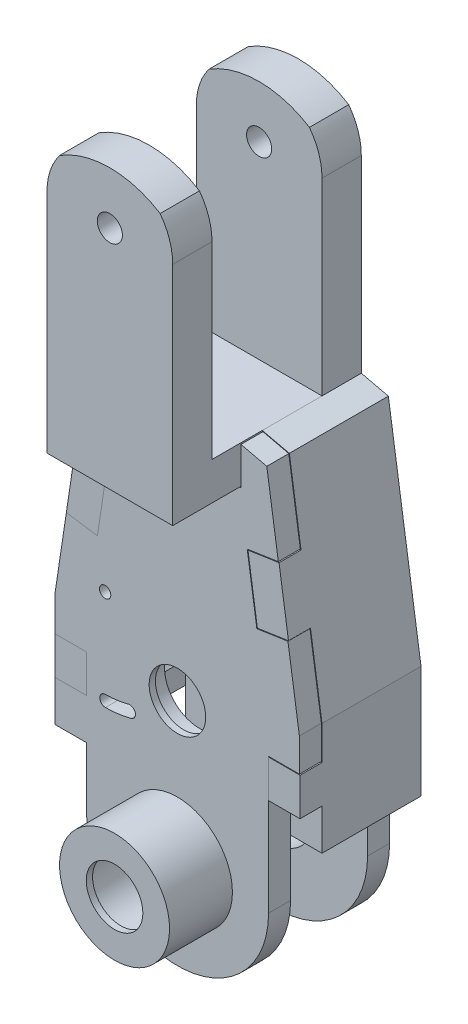
SolidWorks part; units mm, degrees
note: The reader was unsure of these and kept them because the rebuilt part matched: shared geometry of "Sketch1<3>", "Sketch2<3>", "Sketch5<3>", "Sketch12<5>", "Sketch12<6>".
ref_plane "Front Plane" through (0, 0, 0) normal (0, 0, 1) x (1, 0, 0)
ref_plane "Top Plane" through (0, 0, 0) normal (0, 1, 0) x (1, 0, 0)
ref_plane "Right Plane" through (0, 0, 0) normal (1, 0, 0) x (0, 0, -1)
sketch "Sketch1" plane through (0, 0, 0) normal (0, 0, 1) x (1, 0, 0)
  line L0 (20, -72) -> (-20, -72)
  line L1 (-20, -72) -> (-20, 0)
  line L2 (20, 0) -> (20, -72)
  line L3 (-20, -60) -> (20, -60)
  arc A0 (-20, 0) -> (20, 0) centre (0, 0) cw
  circle A1 centre (0, 0) radius 4
  arc A2 (-16, 12) -> (16, 12) centre (0, -13.3772) cw
  point P12 (0, 0)
  dimension "D1" = 20
  dimension "D3" = 8
  dimension "D5" = 30
  dimension "D2" = 60
  dimension "D4" = 12
  dimension "D6" = 12
extrude "Boss-Extrude1" add sketch "Sketch1" along normal mid plane 60 contours A0 L1 L3 L2 A1 | L3 L1 L0 L2
extrude "Cut-Extrude1" cut sketch "Sketch1<3>" against normal mid plane 35 contours A0 L1 L3 L2 A1
sketch "Sketch1<3>" plane through (0, 0, 0) normal (0, 0, 1) x (1, 0, 0) same geometry as "Sketch1"
sketch "Sketch2" plane through (0, 0, -30) normal (0, 0, -1) x (-1, 0, 0)
  line L0 (-29, -132) -> (-29, -167)
  line L10 (-29, -167) -> (-39, -167)
  line L12 (29, -167) -> (39, -167)
  line L17 (0, 0) -> (0, -236.1713) construction
  line L18 (-20, -72) -> (-29, -132)
  line L22 (20, -72) -> (29, -132)
  line L23 (-20, -72) -> (20, -72)
  line L24 (-39, -131.2542) -> (-39, -185)
  line L26 (39, -131.2542) -> (39, -185)
  line L27 (28.6119, -62) -> (39, -131.2542)
  line L29 (-28.6119, -62) -> (-39, -131.2542)
  line L30 (-28.6119, -62) -> (28.6119, -62) construction
  line L31 (-28.6119, -62) -> (-20, -60)
  line L32 (-20, 0) -> (-20, -72) construction
  line L33 (28.6119, -62) -> (20, -60)
  line L34 (-20, -60) -> (20, -60)
  line L35 (-39, -185) -> (39, -185) construction
  line L36 (-29, -175) -> (29, -175) construction
  line L37 (29, -132) -> (29, -175) construction
  line L38 (-29, -132) -> (-29, -175) construction
  line L39 (29, -132) -> (29, -167)
  line L40 (-29, -167) -> (-29, -185)
  line L41 (29, -167) -> (29, -185)
  circle A0 centre (0, -185) radius 11.1 construction
  arc A2 (39, -185) -> (-39, -185) centre (0, -185) cw construction
  arc A3 (-29, -185) -> (29, -185) centre (0, -185) ccw
  point P10 (0, -185)
  dimension "D6" = 22.2
  dimension "D5" = 35
  dimension "D1" = 58
  dimension "D2" = 60
  dimension "D3" = 10
  dimension "D4" = 12
  dimension "D7" = 185
extrude "Boss-Extrude2" add sketch "Sketch2" against normal blind 7
extrude "Boss-Extrude3" add sketch "Sketch2<3>" against normal blind 31.5
sketch "Sketch2<3>" plane through (0, 0, -30) normal (0, 0, -1) x (-1, 0, 0) same geometry as "Sketch2"
sketch "Sketch4" plane through (0, 0, -23) normal (0, 0, 1) x (1, 0, 0)
  line L0 (20, -72) -> (-20, -72) construction
  line L1 (-21, -114) -> (21, -114)
  line L2 (-21, -114) -> (-21, -72)
  line L3 (-21, -72) -> (21, -72)
  line L4 (21, -114) -> (21, -72)
  line L5 (-21, -114) -> (21, -72) construction
  line L6 (-21, -72) -> (21, -114) construction
  line L7 (-15.5, -108.5) -> (15.5, -108.5) construction
  line L8 (-15.5, -108.5) -> (-15.5, -77.5) construction
  line L9 (-15.5, -77.5) -> (15.5, -77.5) construction
  line L10 (15.5, -108.5) -> (15.5, -77.5) construction
  line L11 (-15.5, -108.5) -> (15.5, -77.5) construction
  line L12 (-15.5, -77.5) -> (15.5, -108.5) construction
  line L13 (15.5, -112) -> (15.5, -105) construction
  line L14 (13.7, -112) -> (13.7, -105)
  line L15 (17.3, -112) -> (17.3, -105)
  line L16 (15.5, -81) -> (15.5, -74) construction
  line L17 (13.7, -81) -> (13.7, -74)
  line L18 (17.3, -81) -> (17.3, -74)
  line L19 (-15.5, -81) -> (-15.5, -74) construction
  line L20 (-17.3, -81) -> (-17.3, -74)
  line L21 (-13.7, -81) -> (-13.7, -74)
  line L22 (-15.5, -112) -> (-15.5, -105) construction
  line L23 (-17.3, -112) -> (-17.3, -105)
  line L24 (-13.7, -112) -> (-13.7, -105)
  line L25 (0, -96.5) -> (0, -89.5) construction
  line L26 (-11.1, -96.5) -> (-11.1, -89.5)
  line L27 (11.1, -96.5) -> (11.1, -89.5)
  arc A0 (13.7, -112) -> (17.3, -112) centre (15.5, -112) ccw
  arc A1 (17.3, -105) -> (13.7, -105) centre (15.5, -105) ccw
  arc A2 (13.7, -81) -> (17.3, -81) centre (15.5, -81) ccw
  arc A3 (17.3, -74) -> (13.7, -74) centre (15.5, -74) ccw
  arc A4 (-17.3, -81) -> (-13.7, -81) centre (-15.5, -81) ccw
  arc A5 (-13.7, -74) -> (-17.3, -74) centre (-15.5, -74) ccw
  arc A6 (-17.3, -112) -> (-13.7, -112) centre (-15.5, -112) ccw
  arc A7 (-13.7, -105) -> (-17.3, -105) centre (-15.5, -105) ccw
  arc A8 (-11.1, -96.5) -> (11.1, -96.5) centre (0, -96.5) ccw
  arc A9 (11.1, -89.5) -> (-11.1, -89.5) centre (0, -89.5) ccw
  point P0 (0, -93)
  point P5 (0, -93)
  point P15 (15.5, -108.5)
  point P21 (15.5, -77.5)
  point P28 (-15.5, -77.5)
  point P35 (-15.5, -108.5)
  point P43 (0, -93)
  dimension "D4" = 1.8
  dimension "D6" = 11.1
  dimension "D1" = 42
  dimension "D2" = 21
  dimension "D3" = 31
  dimension "D5" = 7
  dimension "D7" = 7
extrude "Cut-Extrude2" cut sketch "Sketch4" against normal through all contours L24 A7 L23 A6 | L15 A1 L14 A0 | L18 A3 L17 A2 | L27 A9 L26 A8 | L21 A5 L20 A4
sketch "Sketch5" plane through (0, 0, -23) normal (0, 0, 1) x (1, 0, 0)
  circle A0 centre (0, -141) radius 11.1
  circle A1 centre (0, -185) radius 11.1
  circle A2 centre (0, -141) radius 9
  circle A3 centre (0, -185) radius 9
  point P8 (0, 0)
  dimension "D2" = 22.2
  dimension "D4" = 22.2
  dimension "D5" = 18
  dimension "D6" = 18
  dimension "D1" = 48
  dimension "D3" = 44
extrude "Cut-Extrude3" cut sketch "Sketch5" against normal through all contours A3 | A2
extrude "Cut-Extrude4" cut sketch "Sketch5<3>" against normal blind 5
sketch "Sketch5<3>" plane through (0, 0, -23) normal (0, 0, 1) x (1, 0, 0) same geometry as "Sketch5"
sketch "Sketch8" plane through (0, 0, 1.5) normal (0, 0, 1) x (1, 0, 0)
  line L0 (0, -54.5477) -> (0, -241.8797) construction
  line L1 (-22.4398, -88.2655) -> (-32.3292, -86.7821)
  line L2 (-20, -72) -> (-29, -132) construction
  line L3 (-28.6119, -62) -> (-39, -131.2542) construction
  line L4 (-32.3292, -86.7821) -> (-35.3292, -106.7821)
  line L5 (-35.3292, -106.7821) -> (-25.4398, -108.2655)
  line L6 (-20, -72) -> (-29, -132) construction
  line L7 (-25.4398, -108.2655) -> (-22.4398, -88.2655)
  line L8 (-39, -131.2542) -> (-39, -167) construction
  line L9 (-39, -142) -> (-29, -142)
  line L10 (-39, -142) -> (-39, -154)
  line L11 (-39, -154) -> (-29, -154)
  line L12 (-29, -142) -> (-29, -154)
  line L13 (-29, -132) -> (-29, -167) construction
  line L14 (29, -142) -> (29, -154)
  line L15 (39, -154) -> (29, -154)
  line L16 (39, -142) -> (39, -154)
  line L17 (39, -142) -> (29, -142)
  line L18 (25.4398, -108.2655) -> (22.4398, -88.2655)
  line L19 (35.3292, -106.7821) -> (25.4398, -108.2655)
  line L20 (32.3292, -86.7821) -> (35.3292, -106.7821)
  line L21 (22.4398, -88.2655) -> (32.3292, -86.7821)
  point P21 (-22.0154, -85.436)
  point P23 (-22.3566, -87.7108)
  dimension "D1" = 12
  dimension "D2" = 20
  dimension "D3" = 10
  dimension "D4" = 24
extrude "Boss-Extrude4" add sketch "Sketch8" along normal blind 7
sketch "Sketch11" plane through (0, 0, 1.5) normal (0, 0, 1) x (1, 0, 0)
  line L0 (0, -35.9893) -> (0, -185) construction
  line L1 (-20, -72) -> (-20, -60)
  line L2 (-20, -60) -> (-28.6119, -62)
  line L3 (-28.6119, -62) -> (-32.3292, -86.7821)
  line L4 (-32.3292, -86.7821) -> (-22.4398, -88.2655)
  line L5 (-25.4398, -108.2655) -> (-35.3292, -106.7821)
  line L6 (-35.3292, -106.7821) -> (-39, -131.2542)
  line L7 (-39, -131.2542) -> (-39, -142)
  line L8 (-39, -142) -> (-29, -142)
  line L9 (-29, -154) -> (-29, -142) construction
  line L10 (-29, -132) -> (-29, -167) construction
  line L11 (-29, -154) -> (-39, -154)
  line L12 (-39, -154) -> (-39, -167)
  line L13 (-39, -167) -> (-29, -167)
  line L14 (29, -167) -> (29, -185) construction
  line L15 (-29, -167) -> (-29, -185) construction
  line L16 (29, -167) -> (29, -185)
  line L17 (-29, -167) -> (-29, -185)
  line L18 (29, -167) -> (29, -185)
  line L19 (-29, -167) -> (-29, -185)
  line L20 (39, -167) -> (29, -167)
  line L21 (39, -154) -> (39, -167)
  line L22 (29, -154) -> (39, -154)
  line L23 (39, -142) -> (29, -142)
  line L24 (39, -131.2542) -> (39, -142)
  line L25 (35.3292, -106.7821) -> (39, -131.2542)
  line L26 (25.4398, -108.2655) -> (35.3292, -106.7821)
  line L27 (32.3292, -86.7821) -> (22.4398, -88.2655)
  line L28 (28.6119, -62) -> (32.3292, -86.7821)
  line L29 (20, -60) -> (28.6119, -62)
  line L30 (20, -72) -> (20, -60)
  line L31 (20, -72) -> (-20, -72)
  line L32 (-22.4398, -88.2655) -> (-25.4398, -108.2655)
  line L33 (-29, -142) -> (-29, -154)
  line L34 (22.4398, -88.2655) -> (25.4398, -108.2655)
  line L35 (29, -132) -> (29, -167)
  line L36 (25.4398, -108.2655) -> (29, -132) construction
  line L37 (20, -72) -> (29, -132) construction
  line L38 (38.8, -141.8) -> (29, -141.8)
  line L39 (38.8, -131.2691) -> (38.8, -141.8)
  line L40 (35.1611, -107.0096) -> (38.8, -131.2691)
  line L41 (25.2717, -108.493) -> (35.1611, -107.0096)
  line L42 (22.2124, -88.0974) -> (25.2717, -108.493)
  line L43 (32.1017, -86.614) -> (22.2124, -88.0974)
  line L44 (28.4342, -62.1641) -> (32.1017, -86.614)
  line L45 (20.2, -60.2518) -> (28.4342, -62.1641)
  line L46 (20.2, -72.2) -> (20.2, -60.2518)
  line L47 (20.2, -72.2) -> (-20.2, -72.2)
  line L48 (-20.2, -72.2) -> (-20.2, -60.2518)
  line L49 (-20.2, -60.2518) -> (-28.4342, -62.1641)
  line L50 (-28.4342, -62.1641) -> (-32.1017, -86.614)
  line L51 (-32.1017, -86.614) -> (-22.2124, -88.0974)
  line L52 (-22.2124, -88.0974) -> (-25.2717, -108.493)
  line L53 (-25.2717, -108.493) -> (-35.1611, -107.0096)
  line L54 (-35.1611, -107.0096) -> (-38.8, -131.2691)
  line L55 (-38.8, -131.2691) -> (-38.8, -141.8)
  line L56 (-38.8, -141.8) -> (-28.8, -141.8)
  line L57 (-28.8, -141.8) -> (-28.8, -154.2)
  line L58 (-28.8, -154.2) -> (-38.8, -154.2)
  line L59 (-38.8, -154.2) -> (-38.8, -166.8)
  line L60 (-38.8, -166.8) -> (-28.8, -166.8)
  line L61 (-28.8, -166.8) -> (-28.8, -185)
  line L62 (28.8, -167) -> (28.8, -185)
  line L63 (29.2, -167) -> (29.2, -185)
  line L64 (-28.8, -167) -> (-28.8, -185)
  line L65 (29, -153.8) -> (39.2, -153.8)
  line L66 (39.2, -153.8) -> (39.2, -167.2)
  line L67 (39.2, -167.2) -> (29, -167.2)
  line L68 (29.2, -132) -> (29.2, -167)
  arc A0 (-29, -185) -> (29, -185) centre (0, -185) ccw construction
  arc A1 (-29, -185) -> (29, -185) centre (0, -185) ccw
  arc A2 (-28.8, -185) -> (28.8, -185) centre (0, -185) ccw
  point P57 (29, -132)
  dimension "D1" = 0.2
extrude "Boss-Extrude6" add sketch "Sketch11" along normal blind 7 separate body
sketch "Sketch13" plane through (0, 0, 8.5) normal (0, 0, 1) x (1, 0, 0)
  circle A0 centre (0, -185) radius 17.5
  dimension "D1" = 35
extrude "Boss-Extrude7" add sketch "Sketch13" along normal blind 20
sketch "Sketch12" plane through (0, 0, 1.5) normal (0, 0, -1) x (-1, 0, 0)
  circle A1 centre (0, -185) radius 9
  circle A2 centre (0, -185) radius 9
  circle A3 centre (0, -141) radius 9
  circle A4 centre (0, -141) radius 9
  circle A5 centre (0, -185) radius 11.1
  circle A6 centre (0, -185) radius 11.1
  circle A7 centre (0, -141) radius 11.1
  circle A8 centre (0, -141) radius 11.1
  dimension "D1" = 0
  dimension "D2" = 0
  dimension "D3" = 0
  dimension "D4" = 0
extrude "Cut-Extrude5" cut sketch "Sketch12" against normal through all contours A4 | A2
extrude "Cut-Extrude7" cut sketch "Sketch12<5>" against normal offset from surface (25 mm away) 2 contours A6 A2 up to face at (9, -185, 28.5)
sketch "Sketch12<5>" plane through (0, 0, 1.5) normal (0, 0, -1) x (-1, 0, 0) same geometry as "Sketch12"
extrude "Cut-Extrude8" cut sketch "Sketch12<6>" against normal blind 5 contours A8 A4
sketch "Sketch12<6>" plane through (0, 0, 1.5) normal (0, 0, -1) x (-1, 0, 0) same geometry as "Sketch12"
sketch "Sketch14" plane through (0, 0, 8.5) normal (0, 0, 1) x (1, 0, 0)
  line L0 (-23, -122.5) -> (-22.915, -152.4999) construction
  line L1 (-23, -122.5) -> (-15.1534, -151.4557) construction
  line L2 (-23, -122.5) -> (-19, -152.2321) construction
  line L4 (-39, -154) -> (-39, -167) construction
  circle A0 centre (0, -141) radius 8.15 construction
  circle A1 centre (0, -185) radius 25.65 construction
  circle A2 centre (-23, -122.5) radius 1.8
  arc A3 (-22.915, -152.4999) -> (-15.1534, -151.4557) centre (-23, -122.5) ccw construction
  arc A4 (-22.9099, -154.2999) -> (-14.6826, -153.193) centre (-23, -122.5) ccw
  arc A5 (-22.9201, -150.6999) -> (-15.6242, -149.7183) centre (-23, -122.5) ccw
  arc A6 (-22.9201, -150.6999) -> (-22.9099, -154.2999) centre (-22.915, -152.4999) ccw
  arc A7 (-14.6826, -153.193) -> (-15.6242, -149.7183) centre (-15.1534, -151.4557) ccw
  point P12 (-19, -152.2321)
  point P17 (0, 0)
  point P18 (0, 0)
  point P19 (-17.7975, -154.6031)
  point P20 (-17.2186, -155.2212)
  point P21 (-20.4913, -131.5922)
  point P22 (-22.9132, -125.505)
  point P23 (-17.1532, -155.2867)
  point P24 (-16.0193, -154.919)
  dimension "D1" = 51.3
  dimension "D2" = 16.3
  dimension "D3" = 3.6
  dimension "D4" = 1.8
  dimension "D6" = 30
  dimension "D5" = 15
  dimension "D7" = 18.5
  dimension "D8" = 23
  dimension "D9" = 20
extrude "Cut-Extrude9" cut sketch "Sketch14" against normal up to surface (7 mm away) contours A4 A7 A5 A6 | A2 up to face at (-11.1, -141, 1.5)
sketch "Sketch15" plane through (0, 0, -23) normal (0, 0, 1) x (1, 0, 0)
  line L1 (-29, -154) -> (-29, -167) construction
  line L2 (-29, -132) -> (-29, -167) construction
  line L4 (-29, -145) -> (-29, -160)
  arc A0 (-29, -145) -> (-29, -160) centre (-20.9533, -152.5) ccw
  dimension "D1" = 11
  dimension "D2" = 15
  dimension "D3" = 22.5
extrude "Cut-Extrude10" cut sketch "Sketch15" along normal up to surface (24.5 mm away) up to face at (-34, -160.5, 1.5)
